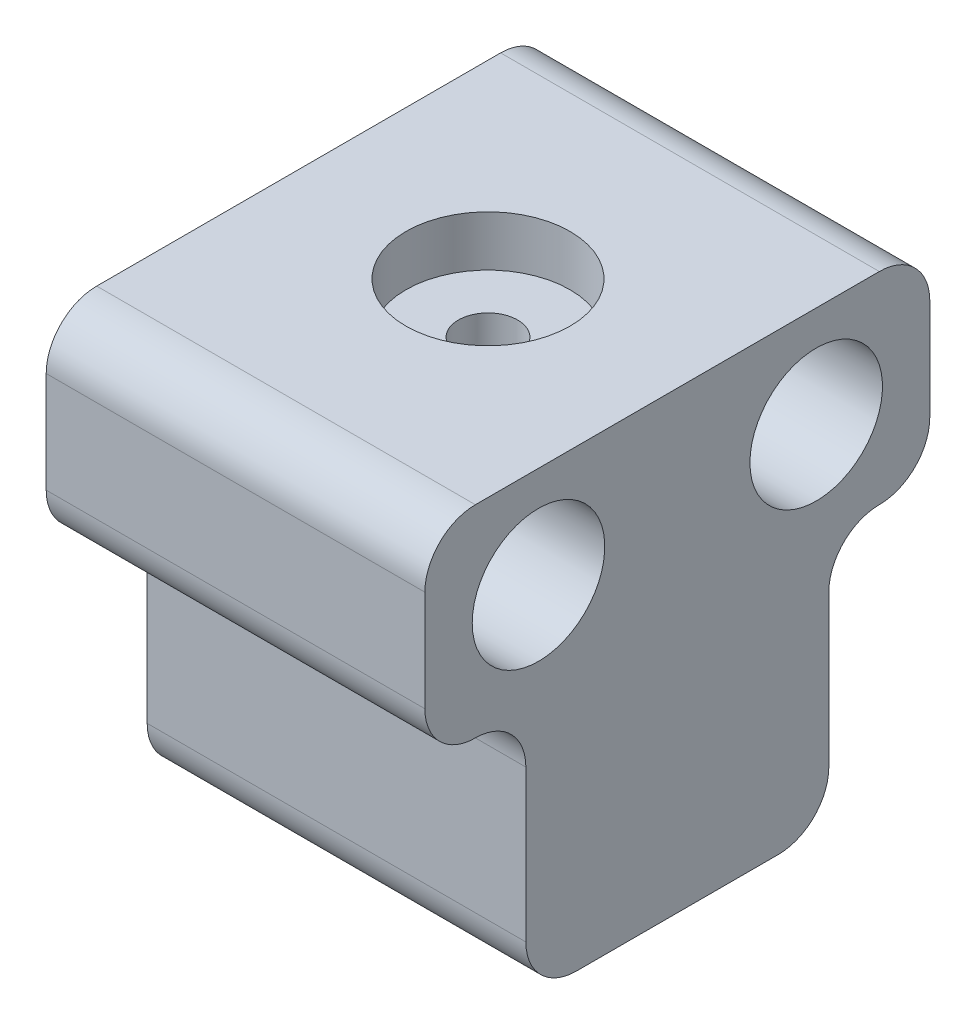
SolidWorks part; units mm, degrees
ref_plane "Front Plane" through (0, 0, 0) normal (0, 0, 1) x (1, 0, 0)
ref_plane "Top Plane" through (0, 0, 0) normal (0, 1, 0) x (1, 0, 0)
ref_plane "Right Plane" through (0, 0, 0) normal (1, 0, 0) x (0, 0, -1)
sketch "Sketch1" plane through (0, 0, 0) normal (0, 1, 0) x (1, 0, 0)
  line L1 (-15, 8.1101) -> (15, 8.1101)
  line L2 (-15, 8.1101) -> (-15, -31.8899)
  line L4 (15, 8.1101) -> (15, -31.8899)
  line L7 (-15, -31.8899) -> (15, -31.8899)
  point P4 (0, 8.1101)
  dimension "D1" = 30
  dimension "D3" = 40
extrude "Boss-Extrude1" add sketch "Sketch1" along normal blind 36
sketch "Sketch2" plane through (0, 36, 0) normal (0, -1, 0) x (1, 0, 0)
  line L0 (15, 31.8899) -> (15, -8.1101) construction
  line L1 (-11.25, 21.3899) -> (-5.5, 21.3899)
  line L2 (-11.25, 21.3899) -> (-11.25, 2.3899)
  line L3 (-11.25, 2.3899) -> (-5.5, 2.3899)
  line L4 (11.25, 21.3899) -> (11.25, 2.3899)
  line L7 (-5.5, 2.3899) -> (-5.5, 5.3899)
  line L8 (-5.5, 5.3899) -> (5.5, 5.3899)
  line L9 (5.5, 2.3899) -> (5.5, 5.3899)
  line L10 (-15, -8.1101) -> (-15, 31.8899) construction
  line L11 (15, 31.8899) -> (15, -8.1101) construction
  line L12 (5.5, 2.3899) -> (11.25, 2.3899)
  line L14 (5.5, 21.3899) -> (11.25, 21.3899)
  line L16 (-5.5, 21.3899) -> (-5.5, 18.3899)
  line L17 (-5.5, 18.3899) -> (5.5, 18.3899)
  line L18 (5.5, 21.3899) -> (5.5, 18.3899)
  point P10 (15, 11.8899)
  point P16 (0, 5.3899)
  dimension "D1" = 9.5
  dimension "D2" = 3.75
  dimension "D3" = 3.75
  dimension "D4" = 3
  dimension "D5" = 11
  dimension "D6" = 19
extrude "Cut-Extrude1" cut sketch "Sketch2" along normal through all from offset 14
sketch "Sketch4" plane through (0, 36, 0) normal (0, 1, 0) x (1, 0, 0)
  line L1 (-15, 8.1101) -> (-15, -31.8899) construction
  circle A0 centre (0, -11.8899) radius 2.35
  point P5 (-15, -11.8899)
  dimension "D1" = 4.7
extrude "Cut-Extrude3" cut sketch "Sketch4" against normal through all
sketch "Sketch5" plane through (0, 36, 0) normal (0, 1, 0) x (1, 0, 0)
  circle A0 centre (0, -11.8899) radius 6.5
  dimension "D1" = 13
extrude "Cut-Extrude4" cut sketch "Sketch5" against normal blind 4
sketch "Sketch10" plane through (0, 32, 0) normal (0, 1, 0) x (1, 0, 0)
  circle A0 centre (0, -11.8899) radius 4.4281
extrude "Boss-Extrude4" [suppressed] add sketch "Sketch10" against normal blind 0.65
sketch "Sketch12" plane through (-15, 0, 0) normal (-1, 0, 0) x (0, 0, 1)
  line L0 (-8.1101, 36) -> (31.8899, 36) construction
  line L2 (-8.1101, 0) -> (-0.1101, 0)
  line L3 (-8.1101, 0) -> (-8.1101, 20)
  line L4 (-8.1101, 20) -> (-0.1101, 20)
  line L5 (-0.1101, 0) -> (-0.1101, 20)
  line L6 (31.8899, 0) -> (23.8899, 0)
  line L7 (31.8899, 0) -> (31.8899, 20)
  line L8 (31.8899, 20) -> (23.8899, 20)
  line L9 (23.8899, 0) -> (23.8899, 20)
  circle A0 centre (0.8899, 28) radius 5.25
  circle A1 centre (22.8899, 28) radius 5.25
  point P8 (11.8899, 36)
  dimension "D2" = 10.5
  dimension "D1" = 22
  dimension "D3" = 11
  dimension "D4" = 8
  dimension "D5" = 16
  dimension "D6" = 8
extrude "Cut-Extrude5" cut sketch "Sketch12" against normal through all
fillet "Fillet1" radius 4 8 edges at (0, 0, 23.8899) (0, 0, -0.1101) (0, 20, -0.1101) (0, 20, -8.1101) (0, 36, -8.1101) (0, 36, 31.8899) (0, 20, 31.8899) (0, 20, 23.8899)
